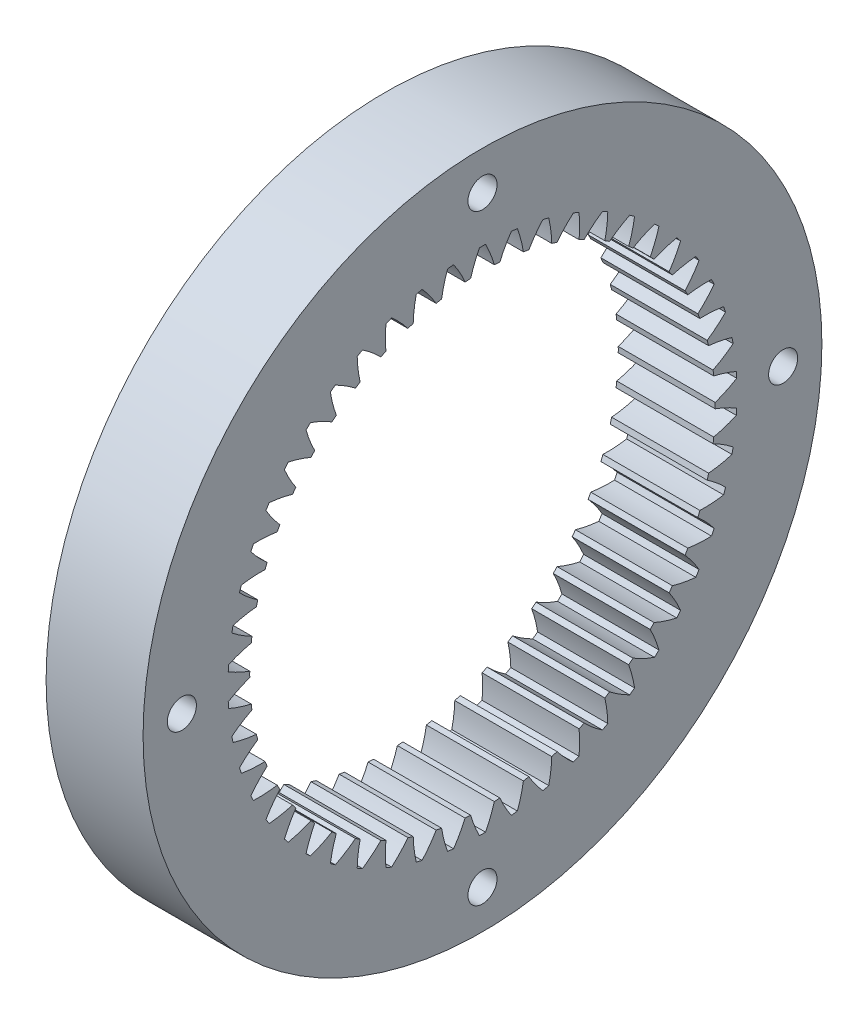
SolidWorks part; units mm, degrees
ref_plane "Plane1" through (0, 0, 0) normal (0, 0, 1) x (1, 0, 0)
ref_plane "Plane2" through (0, 0, 0) normal (0, 1, 0) x (1, 0, 0)
ref_plane "Plane3" through (0, 0, 0) normal (1, 0, 0) x (0, 0, -1)
other "Configuration Table"
sketch "HoldingSke" plane through (0, 0, 0) normal (0, 1, 0) x (1, 0, 0)
  line L0 (0, 0) -> (0.6428, -0.766)
  line L1 (-15, 0) -> (100, 0) construction
  line L2 (0, 0) -> (-2.1039, 2.3779)
  line L3 (0, 0) -> (-11.863, 4.5341)
  line L4 (0, 0) -> (5.5511, 6.6156)
  line L5 (0, 0) -> (-23.7986, -8.8762)
  line L6 (0, 0) -> (-10.5278, -7.1032)
  line L7 (-2.1039, 2.3779) -> (3.3635, 27.1825)
  line L8 (-76.2, 3.3779) -> (-54.61, 3.3779)
  line L9 (-71.009, 38.7566) -> (-53.1078, 45.2721)
  line L10 (-76.2, 71.12) -> (104.1128, 71.12)
  line L11 (0, 0) -> (-10, 0)
  line L12 (-76.2, 101.6) -> (-76.162, 101.6)
  line L13 (24.9733, 27.94) -> (52.9518, 28.4284)
  line L14 (24.9733, 27.94) -> (24.9743, 27.94)
  line L15 (24.9733, 27.94) -> (100.4006, 29.5858)
  circle A0 centre (0, 0) radius 30
  circle A1 centre (0, 0) radius 12.7
  circle A2 centre (0, 0) radius 12.7
  dimension "Num_teeth" = 50
  dimension "Pitch_radius" = 180.3128
  dimension "Width" = 10
  dimension "Diameter" = 60
sketch "BasProSke" plane through (0, 0, 0) normal (0, 1, 0) x (1, 0, 0)
  line L0 (-10, 0) -> (60, 0) construction
  line L1 (0, 24) -> (0, 30)
  line L2 (0, 24) -> (10, 24)
  line L3 (10, 24) -> (10, 30)
  line L4 (10, 30) -> (0, 30)
  dimension "Thickness" = 10
  dimension "Diameter" = 60
revolve "Base-Revolve" add sketch "BasProSke" angle 360 about L0
sketch "TooCutSke" plane through (0, 0, 0) normal (1, 0, 0) x (0, 0, -1)
  line L3 (0.8803, 24.9845) -> (0.8803, 53.6633) construction
  line L4 (0, 0) -> (0, 59.563) construction
  line L5 (0, 0) -> (-4.2903, 68.1927) construction
  line L6 (-10.7899, 20.506) -> (36.4405, 23.4775) construction
  circle A0 centre (0, 0) radius 25 construction
  circle A1 centre (0, 0) radius 26.251 construction
  circle A2 centre (0, 0) radius 21.1431 construction
  circle A3 centre (0, 0) radius 23.9746 construction
  arc A4 (1.2282, 23.9431) -> (0.3126, 26.2491) centre (-10.7899, 20.506) ccw
  arc A5 (1.2282, 23.9431) -> (-1.2282, 23.9431) centre (0, 0) ccw
  arc A6 (0.3126, 26.2491) -> (-0.3126, 26.2491) centre (0, 0) ccw
  arc A7 (-0.3126, 26.2491) -> (-1.2282, 23.9431) centre (10.7899, 20.506) ccw
extrude "ToothCut" cut sketch "TooCutSke" along normal through all
fillet "Breaks" [suppressed] radius 0.1
fillet "RootFillets" [suppressed] radius 0.251
pattern_circular "TeethCuts" count 50 every 7.2 about axis through (-10, 0, 0) along (1, 0, 0) of "RootFillets", "Breaks", "ToothCut"
sketch "Sketch1" plane through (10, 0, 0) normal (1, 0, 0) x (0, 0, -1)
  circle A0 centre (0, 0) radius 30
  circle A1 centre (0, 0) radius 35
  dimension "D1" = 5
extrude "Boss-Extrude1" add sketch "Sketch1" against normal blind 10
sketch "Sketch2" plane through (10, 0, 0) normal (1, 0, 0) x (0, 0, -1)
  line L0 (0, 0) -> (0, 31) construction
  circle A0 centre (0, 0) radius 35
  circle A1 centre (0, 0) radius 31
  circle A2 centre (0, 31) radius 1.5
  circle A3 centre (31, 0) radius 1.5
  circle A4 centre (0, -31) radius 1.5
  circle A5 centre (-31, 0) radius 1.5
  point P16 (0, 0)
  dimension "D2" = 4
  dimension "D1" = 4
extrude "Cut-Extrude1" cut sketch "Sketch2" against normal blind 10 contours A1 A3 | A1 A5 | A2 | A4 | A3 | A5 region at (10, 0, -31.63) region at (10, 0, 31.63)
equation "' \"Module@HoldingSke\" = 6.35"
equation "' \"Num_teeth@HoldingSke\" = 24"
equation "' \"Ap@HoldingSke\" =  14.5"
equation "' \"Ap@HoldingSke\" = 14.5"
equation "' \"Width@HoldingSke\" = 12"
equation "' \"Diameter@HoldingSke\" = 8 * 25.4"
equation "' \"Show_teeth@HoldingSke\" = 100"
equation "' \"Backlash@HoldingSke\" = 0.009 * 25.4"
equation "' \"Addendum_fac@HoldingSke\" = 1.0"
equation "' \"Dedendum_fac@HoldingSke\" = 1.25"
equation "' \"Dedendum_add@HoldingSke\" = 0.00005 * 25.4"
equation "' \"Clearance_fac@HoldingSke\" = 0.25"
equation "\"Pitch@HoldingSke\" = 1 / \"Module@HoldingSke\" "
equation "\"Overcut_dia@TooCutSke\" = (\"Num_teeth@HoldingSke\" - 2 * \"Addendum_fac@HoldingSke\") / \"Pitch@HoldingSke\" - 0.002 * 25.4"
equation "\"Pitch_dia@TooCutSke\" = \"Num_teeth@HoldingSke\" / \"Pitch@HoldingSke\""
equation "\"Base_dia@TooCutSke\" = \"Num_teeth@HoldingSke\" / \"Pitch@HoldingSke\" * cos((\"Ap@HoldingSke\"  * 3.14159265 / 180)) * 0.90"
equation "\"Root_dia@TooCutSke\" = \"Num_teeth@HoldingSke\"  / \"Pitch@HoldingSke\" + 2 *  \"Dedendum_fac@HoldingSke\"/ \"Pitch@HoldingSke\" + \"Dedendum_add@HoldingSke\" * 2"
equation "\"Half_ang@TooCutSke\" = 180 / \"Num_teeth@HoldingSke\""
equation "\"Half_CT@TooCutSke\" = \"Num_teeth@HoldingSke\" / \"Pitch@HoldingSke\" * sin((3.14159265 / 2 / \"Num_teeth@HoldingSke\")) / 2 + 10 * \"Backlash@HoldingSke\" / 4"
equation "\"Flank_rad@TooCutSke\" = \"Num_teeth@HoldingSke\" / \"Pitch@HoldingSke\" / 4"
equation "\"Radius@RootFillets\"= \"Clearance_fac@HoldingSke\" / \"Pitch@HoldingSke\" + \"Dedendum_add@HoldingSke\""
equation "\"Break_rad@Breaks\" = 0.02 / \"Pitch@HoldingSke\" * 5"
equation "\"Num_teeth@TeethCuts\" = int( \"Show_teeth@HoldingSke\" ) + 1"
equation "\"Num_teeth@TeethCuts\" = ((sgn( \"Num_teeth@TeethCuts\" - \"Num_teeth@HoldingSke\" )-1)*( \"Num_teeth@TeethCuts\" - \"Num_teeth@HoldingSke\" ))/-2+ \"Num_teeth@HoldingSke\""
equation "\"Num_teeth@TeethCuts\" = ((sgn( \"Num_teeth@TeethCuts\" - 2.0)+1)*( \"Num_teeth@TeethCuts\" - 2.0))/2 +2.0"
equation "\"Angle@TeethCuts\" = 360.0 / \"Num_teeth@HoldingSke\""
equation "\"Diameter@BasProSke\" = \"Num_teeth@HoldingSke\"  / \"Pitch@HoldingSke\" + 2 *  \"Dedendum_fac@HoldingSke\"/ \"Pitch@HoldingSke\" + \"Dedendum_add@HoldingSke\" * 2 + 0.002 * 25.4"
equation "\"Diameter@BasProSke\" = ((sgn( \"Diameter@BasProSke\"  - \"Diameter@HoldingSke\" )+1)*( \"Diameter@BasProSke\"  - \"Diameter@HoldingSke\" ))/2 + \"Diameter@HoldingSke\""
equation "\"Inside_diameter@BasProSke\" =  (\"Num_teeth@HoldingSke\" - 2 * \"Addendum_fac@HoldingSke\") / \"Pitch@HoldingSke\" "
equation "\"Thickness@BasProSke\"  = \"Width@HoldingSke\""
